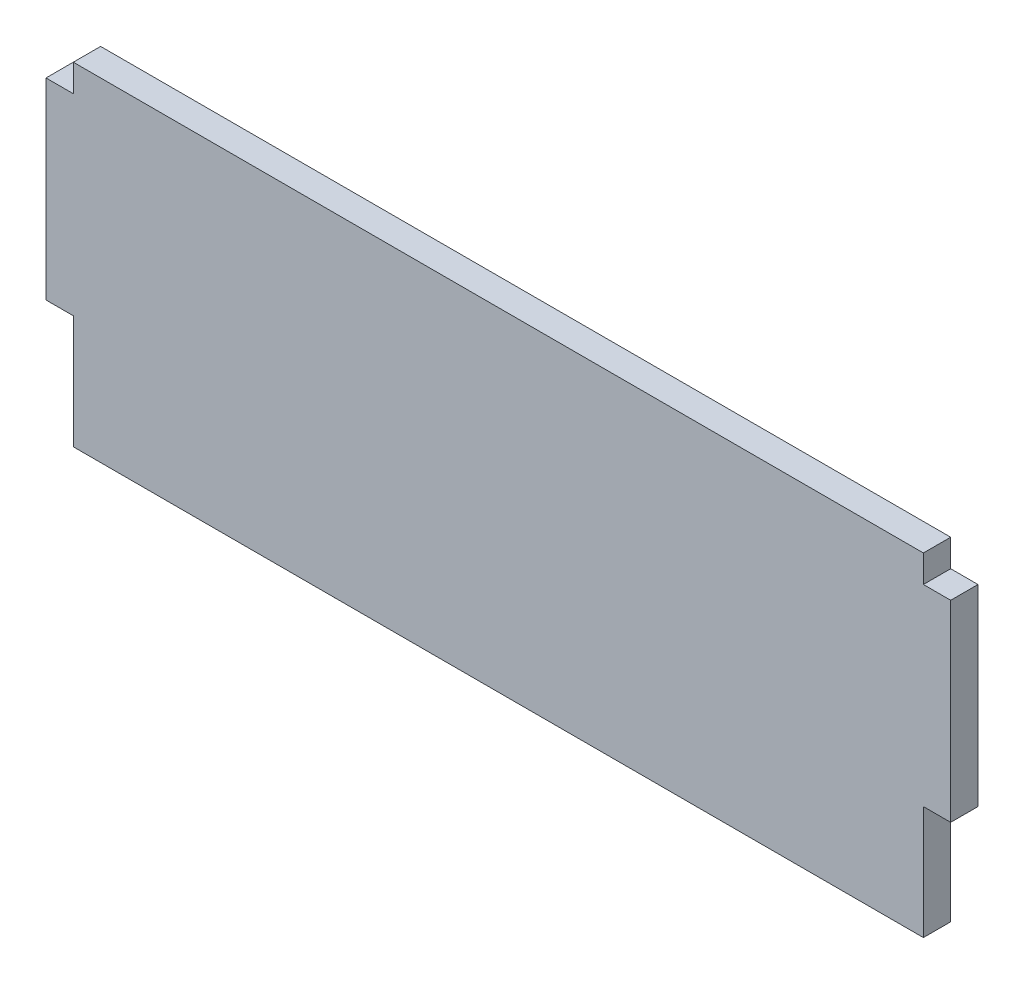
SolidWorks part; units mm, degrees
ref_plane "Front Plane" through (0, 0, 0) normal (0, 0, 1) x (1, 0, 0)
ref_plane "Top Plane" through (0, 0, 0) normal (0, 1, 0) x (1, 0, 0)
ref_plane "Right Plane" through (0, 0, 0) normal (1, 0, 0) x (0, 0, -1)
sketch "Sketch1" plane through (0, 0, 0) normal (0, 0, 1) x (1, 0, 0)
  line L0 (1.8034, 84.963) -> (0, 84.963) construction
  line L1 (1.8034, 84.963) -> (1.8034, 72.263) construction
  line L2 (1.8034, 72.263) -> (0, 72.263) construction
  line L3 (1.8034, 84.963) -> (0, 84.963)
  line L4 (1.8034, 84.963) -> (1.8034, 72.263)
  line L5 (1.8034, 72.263) -> (0, 72.263)
  line L6 (-57.9374, 72.263) -> (-56.134, 72.263) construction
  line L7 (-57.9374, 84.963) -> (-56.134, 84.963) construction
  line L8 (-57.9374, 84.963) -> (-57.9374, 72.263) construction
  line L9 (-57.9374, 72.263) -> (-56.134, 72.263)
  line L10 (-57.9374, 84.963) -> (-56.134, 84.963)
  line L11 (-57.9374, 84.963) -> (-57.9374, 72.263)
  line L12 (-56.134, 84.963) -> (-56.134, 86.7664)
  line L13 (-56.134, 86.7664) -> (0, 86.7664)
  line L14 (0, 86.7664) -> (0, 84.963)
  line L15 (0, 72.263) -> (0, 64.77)
  line L16 (0, 64.77) -> (-56.134, 64.77)
  line L17 (-56.134, 64.77) -> (-56.134, 72.263)
extrude "Boss-Extrude1" add sketch "Sketch1" along normal blind 1.8034
